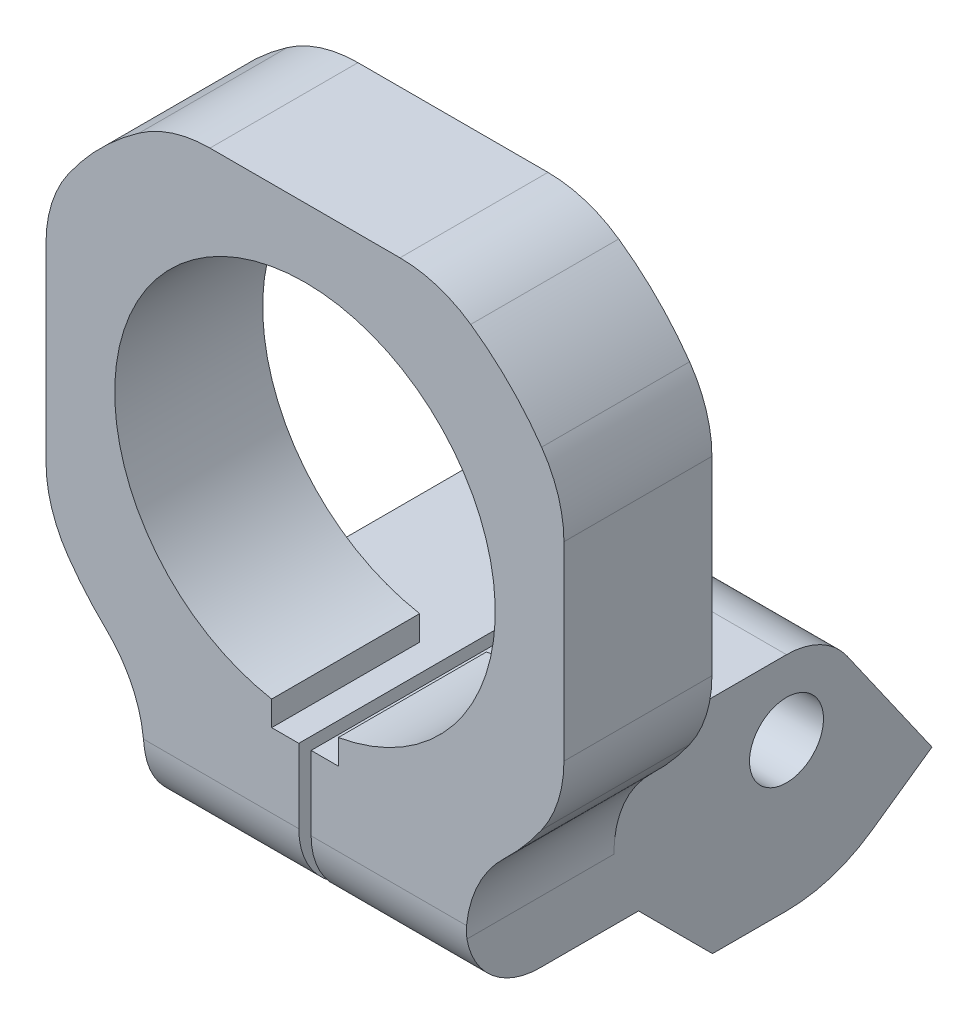
SolidWorks part; units mm, degrees
ref_plane "Front Plane" through (0, 0, 0) normal (0, 0, 1) x (1, 0, 0)
ref_plane "Top Plane" through (0, 0, 0) normal (0, 1, 0) x (1, 0, 0)
ref_plane "Right Plane" through (0, 0, 0) normal (1, 0, 0) x (0, 0, -1)
sketch "Sketch1" plane through (0, 0, 0) normal (0, 0, 1) x (1, 0, 0)
  line L0 (0, 11.4873) -> (0, -15.0157) construction
  line L1 (1.35, -8.5) -> (6.5239, -8.5)
  line L2 (1.35, -8.5) -> (-1.35, -8.5)
  line L3 (1.35, -8.5) -> (1.35, -7.4944)
  line L4 (1.35, -7.4944) -> (-1.35, -7.4944)
  line L5 (-1.35, -8.5) -> (-1.35, -7.4944)
  line L6 (1.35, -8.5) -> (-1.35, -7.4944) construction
  line L7 (1.35, -7.4944) -> (-1.35, -8.5) construction
  line L8 (-1.35, -8.5) -> (-6.5239, -8.5)
  line L9 (-1.35, -8.5) -> (-1.35, -14.6)
  line L10 (-1.35, -14.6) -> (-6.5239, -14.6)
  line L11 (-6.5239, -8.5) -> (-6.5239, -14.6)
  line L12 (1.35, -8.5) -> (1.35, -14.6)
  line L13 (-8.5, -8.5) -> (-1.25, -8.5)
  line L14 (-1.25, -8.5) -> (-1.25, -7.5117)
  line L15 (1.25, -7.5117) -> (1.25, -8.5)
  line L16 (1.25, -8.5) -> (8.5, -8.5)
  line L17 (8.5, -8.5) -> (8.5, -2.45)
  line L18 (8.5, -2.45) -> (10, -2.45)
  line L19 (10, 2.45) -> (8.5, 2.45)
  line L20 (8.5, 2.45) -> (8.5, 8.5)
  line L21 (8.5, 8.5) -> (-8.5, 8.5)
  line L22 (-8.5, 8.5) -> (-8.5, 2.45)
  line L23 (-8.5, 2.45) -> (-10, 2.45)
  line L24 (-10, -2.45) -> (-8.5, -2.45)
  line L25 (-8.5, -2.45) -> (-8.5, -8.5)
  line L26 (-8.5, -8.5) -> (-1.25, -8.5)
  line L27 (-1.25, -8.5) -> (-1.25, -7.5117)
  line L28 (1.25, -7.5117) -> (1.25, -8.5)
  line L29 (1.25, -8.5) -> (8.5, -8.5)
  line L30 (8.5, -8.5) -> (8.5, -2.45)
  line L31 (8.5, -2.45) -> (10, -2.45)
  line L32 (10, 2.45) -> (8.5, 2.45)
  line L33 (8.5, 2.45) -> (8.5, 8.5)
  line L34 (8.5, 8.5) -> (-8.5, 8.5)
  line L35 (-8.5, 8.5) -> (-8.5, 2.45)
  line L36 (-8.5, 2.45) -> (-10, 2.45)
  line L37 (-10, -2.45) -> (-8.5, -2.45)
  line L38 (-8.5, -2.45) -> (-8.5, -8.5)
  line L39 (1.35, -14.6) -> (6.5239, -14.6)
  line L40 (6.5239, -8.5) -> (6.5239, -14.6)
  line L41 (-1.25, -8.0059) -> (-1.35, -8.0059) construction
  line L42 (-1.35, -14.6) -> (-0.25, -14.6)
  line L43 (-1.35, -14.6) -> (-1.35, -8.6)
  line L44 (-1.35, -8.6) -> (-0.25, -8.6)
  line L45 (-0.25, -14.6) -> (-0.25, -8.6)
  line L46 (7.715, 0) -> (7.615, 0) construction
  line L47 (-1.25, -8.5) -> (-1.25, -8.6) construction
  line L48 (-1.35, -8.5) -> (1.35, -8.5)
  line L49 (-1.35, -8.5) -> (-1.35, -8.6)
  line L50 (-1.35, -8.6) -> (1.35, -8.6)
  line L51 (1.35, -8.5) -> (1.35, -8.6)
  line L52 (1.35, -8.6) -> (0.25, -8.6)
  line L53 (0.25, -14.6) -> (0.25, -8.6)
  line L54 (1.35, -14.6) -> (0.25, -14.6)
  circle A0 centre (0, 0) radius 7.715
  circle A1 centre (0, 0) radius 10.715
  arc A3 (1.25, -7.5117) -> (-1.25, -7.5117) centre (0, 0) ccw
  arc A4 (10, -2.45) -> (10, 2.45) centre (10, 0) ccw
  arc A5 (-10, 2.45) -> (-10, -2.45) centre (-10, 0) ccw
  arc A6 (1.25, -7.5117) -> (-1.25, -7.5117) centre (0, 0) ccw
  arc A7 (10, -2.45) -> (10, 2.45) centre (10, 0) ccw
  arc A8 (-10, 2.45) -> (-10, -2.45) centre (-10, 0) ccw
  point P10 (0, -7.9972)
  dimension "D2" = 0.1
  dimension "D4" = 3
  dimension "D3" = 0.5
  dimension "D5" = 6
  dimension "D1" = 0
extrude "Shape" add sketch "Sketch1" along normal blind 6 contours L36 A8 L37 L38 L26 L27 A0 L28 L29 L30 L31 A7 L32 L33 L34 L35 | A7 A1 L33 L32 | A7 L31 L30 A1 | A8 A1 L38 L37 | A8 L36 L35 A1 | L34 A1 | L8 A1 L9 | L12 A1 L1 | A1 L12 L39 L40 | A1 L11 L10 L9 | L9 A1 L45 L44 | A1 L43 L42 L45 | A1 L53 L54 L12 | L53 A1 L12 L50 region at (1.6235, -8.048, 0) region at (3.2599, -9.3092, 0) region at (4.1264, -12.177, 0) region at (0.7964, -9.6403, 0) region at (0.8019, -12.6401, 0) region at (9.2085, -3.9179, 0) region at (-3.2599, -9.3092, 0) region at (-0.7964, -9.6403, 0) region at (-0.8019, -12.6401, 0) region at (9.2085, 3.9179, 0) region at (-4.1264, -12.177, 0) region at (-9.2085, -3.9179, 0) region at (0, 9.3944, 0) region at (-9.2085, 3.9179, 0)
sketch "Sketch3" plane through (0, 0, 0) normal (0, 0, -1) x (-1, 0, 0)
  line L1 (-6.5239, -14.6) -> (-0.25, -14.6)
  line L2 (-6.5239, -14.6) -> (-6.5239, -8.6)
  line L3 (-6.5239, -8.6) -> (-0.25, -8.6)
  line L4 (-0.25, -14.6) -> (-0.25, -8.6)
  line L5 (6.5239, -14.6) -> (0.25, -14.6)
  line L6 (6.5239, -14.6) -> (6.5239, -8.6)
  line L7 (6.5239, -8.6) -> (0.25, -8.6)
  line L8 (0.25, -14.6) -> (0.25, -8.6)
extrude "Lever" add sketch "Sketch3" along normal blind 10
sketch "Sketch2" plane through (6.5239, 0, 0) normal (1, 0, 0) x (0, 0, -1)
  line L0 (-6, -11.6) -> (10, -11.6) construction
  line L4 (10, -8.6) -> (0, -8.6) construction
  line L5 (10, -8.6) -> (-6, -8.6)
  line L6 (10, -8.6) -> (10, -14.6)
  line L7 (10, -14.6) -> (-6, -14.6)
  line L8 (-6, -8.6) -> (-6, -14.6)
  circle A0 centre (7, -11.6) radius 3
  circle A1 centre (7, -11.6) radius 1.5
  circle A2 centre (-3, -11.6) radius 3
  line M4 (-6, -14.6) -> (10, -14.6)
  line M9 (10, -14.6) -> (10, -8.6)
  line M10 (10, -8.6) -> (0, -8.6)
  dimension "D1" = 3
extrude "Cuts" cut sketch "Sketch2" against normal up to surface (13.0478 mm away) contours A0 L6 M10 | A0 L7 M9 | L0 A1 | A1 L0 | A2 L8 M4 region at (6.5239, -13.9299, 5.3299) region at (6.5239, -13.9299, -9.3299) region at (6.5239, -10.9634, -7) region at (6.5239, -12.2366, -7) region at (6.5239, -9.2701, -9.3299) up to face at (-6.5239, -10.5667, -1.3333)
sketch "Sketch5" plane through (-6.5239, 0, 0) normal (-1, 0, 0) x (0, 0, 1)
  line L0 (-7, -17.6) -> (-4, -17.6)
  line L1 (-4, -17.6) -> (-4, -14.6)
  line L2 (3, -14.6) -> (-7, -14.6) construction
  line L3 (-7, -11.6) -> (-10.4415, -16.5149)
  line L4 (-7, -11.6) -> (-7, -14.6) construction
  line L5 (-10.4415, -16.5149) -> (-12.8989, -14.7942)
  line L6 (-12.8989, -14.7942) -> (-9.4575, -9.8793)
  line L7 (-7, -17.6) -> (-7, -14.6)
  line L8 (-4, -17.6) -> (-1, -14.6)
  circle A0 centre (-7, -11.6) radius 6
  arc A1 (-7, -8.6) -> (-7, -14.6) centre (-7, -11.6) ccw construction
  arc M8 (-7, -8.6) -> (-7, -14.6) centre (-7, -11.6) ccw
  line M9 (-7, -14.6) -> (3, -14.6)
  dimension "D1" = 12
  dimension "D2" = 45
  dimension "D3" = 35
extrude "Limits 1" add sketch "Sketch5" against normal up to surface (6.2739 mm away) contours A0 L0 L1 | L7 A0 L1 M9 | L6 A0 L3 M8 | A0 L6 L5 | L3 A0 L7 M8 | A0 L1 L8 M9 | L1 A0 M9 region at (-6.5239, -17.3619, -4.7396) region at (-6.5239, -15.9818, -8.3816) region at (-6.5239, -15.9801, -5.5723) region at (-6.5239, -15.9486, -2.6514) region at (-6.5239, -13.951, -10.5987) region at (-6.5239, -15.0233, -12.1565) region at (-6.5239, -15.3955, -3.2045) up to face at (-0.25, -11.6, -5.5)
sketch "Sketch6" plane through (6.5239, 0, 0) normal (1, 0, 0) x (0, 0, -1)
  line L0 (-3, -14.6) -> (7, -14.6) construction
  line L1 (-3, -14.6) -> (7, -14.6)
  line L7 (-3, -14.6) -> (1, -14.6)
  line L8 (1, -14.6) -> (4, -17.6)
  line L9 (4, -17.6) -> (7, -17.6)
  line L10 (10.4415, -16.5149) -> (12.8989, -14.7942)
  line L11 (12.8989, -14.7942) -> (9.4575, -9.8793)
  line L12 (7, -8.6) -> (-6, -8.6)
  line L13 (-6, -8.6) -> (-6, -11.6)
  line L14 (-3, -14.6) -> (1, -14.6)
  line L15 (1, -14.6) -> (4, -17.6)
  line L16 (4, -17.6) -> (7, -17.6)
  line L17 (10.4415, -16.5149) -> (12.8989, -14.7942)
  line L18 (12.8989, -14.7942) -> (9.4575, -9.8793)
  line L19 (7, -8.6) -> (-6, -8.6)
  line L20 (-6, -8.6) -> (-6, -11.6)
  arc A0 (7, -14.6) -> (7, -8.6) centre (7, -11.6) ccw construction
  arc A1 (7, -14.6) -> (7, -8.6) centre (7, -11.6) ccw
  arc A3 (7, -17.6) -> (10.4415, -16.5149) centre (7, -11.6) ccw
  arc A4 (9.4575, -9.8793) -> (7, -8.6) centre (7, -11.6) ccw
  arc A5 (-6, -11.6) -> (-3, -14.6) centre (-3, -11.6) ccw
  arc A6 (7, -17.6) -> (10.4415, -16.5149) centre (7, -11.6) ccw
  arc A7 (9.4575, -9.8793) -> (7, -8.6) centre (7, -11.6) ccw
  arc A8 (-6, -11.6) -> (-3, -14.6) centre (-3, -11.6) ccw
  arc M13 (7, -14.6) -> (7, -8.6) centre (7, -11.6) ccw
  dimension "D1" = 0
extrude "Limits 2" add sketch "Sketch6" against normal up to surface (6.2739 mm away) contours L16 A6 L17 L18 L1 M13 region at (6.5239, -15.3081, -7.6258) up to face at (0.25, -13.1, -7)
sketch "Sketch8" plane through (0, 0, 6) normal (0, 0, 1) x (1, 0, 0)
  line L1 (-9.5, -9.5) -> (9.5, -9.5)
  line L2 (-9.5, -9.5) -> (-9.5, 9.5)
  line L3 (-9.5, 9.5) -> (9.5, 9.5)
  line L4 (9.5, -9.5) -> (9.5, 9.5)
  line L5 (-9.5, -9.5) -> (9.5, 9.5) construction
  line L6 (-9.5, 9.5) -> (9.5, -9.5) construction
  line L7 (-10.715, -10.715) -> (10.715, -10.715)
  line L8 (-10.715, -10.715) -> (-10.715, 10.715)
  line L9 (-10.715, 10.715) -> (10.715, 10.715)
  line L10 (10.715, -10.715) -> (10.715, 10.715)
  line L11 (-10.715, -10.715) -> (10.715, 10.715) construction
  line L12 (-10.715, 10.715) -> (10.715, -10.715) construction
  arc A0 (6.5239, -8.5) -> (-6.5239, -8.5) centre (0, 0) ccw construction
  point P0 (0, 0)
  point P6 (0, 0)
  arc M16 (6.5239, -8.5) -> (-6.5239, -8.5) centre (0, 0) ccw
  dimension "D1" = 19
extrude "Cut-Extrude2" cut sketch "Sketch8" against normal up to next contours L3 M16 | L2 M16 | L4 M16 region at (-9.9884, 0, 6) region at (9.9884, 0, 6) region at (0, 9.9884, 6)
sketch "Sketch9" plane through (0, 0, 6) normal (0, 0, 1) x (1, 0, 0)
  line L9 (-7.1328, -9.2933) -> (-6.5239, -9.7606)
  line L10 (-6.5239, -8.5) -> (-6.5239, -11.6) construction
  line L11 (7.1328, -9.2933) -> (6.5239, -9.7606)
  line L12 (-10.5, 5.1953) -> (-10.5, -5.1953)
  line L13 (5.1953, 10.5) -> (-5.1953, 10.5)
  line L14 (10.5, -5.1953) -> (10.5, 5.1953)
  line L15 (-10.5, 5.1953) -> (-10.5, -5.1953)
  line L16 (5.1953, 10.5) -> (-5.1953, 10.5)
  line L17 (10.5, -5.1953) -> (10.5, 5.1953)
  line L18 (6.5239, -8.5) -> (6.5239, -11.6) construction
  line L32 (-9.5, 4.9559) -> (-9.5, -4.9559)
  line L33 (-6.5239, -8.5) -> (-6.5239, -11.6)
  line L34 (-6.5239, -11.6) -> (-0.25, -11.6)
  line L35 (-0.25, -11.6) -> (-0.25, -8.6)
  line L36 (-0.25, -8.6) -> (-1.35, -8.6)
  line L37 (-1.35, -8.6) -> (-1.35, -7.596)
  line L38 (1.35, -7.596) -> (1.35, -8.6)
  line L39 (1.35, -8.6) -> (0.25, -8.6)
  line L40 (0.25, -8.6) -> (0.25, -11.6)
  line L41 (0.25, -11.6) -> (6.5239, -11.6)
  line L42 (6.5239, -11.6) -> (6.5239, -8.5)
  line L43 (9.5, -4.9559) -> (9.5, 4.9559)
  line L44 (4.9559, 9.5) -> (-4.9559, 9.5)
  line L45 (-9.5, 4.9559) -> (-9.5, -4.9559)
  line L46 (-6.5239, -8.5) -> (-6.5239, -11.6)
  line L47 (-6.5239, -11.6) -> (-0.25, -11.6)
  line L48 (-0.25, -11.6) -> (-0.25, -8.6)
  line L49 (-0.25, -8.6) -> (-1.35, -8.6)
  line L50 (-1.35, -8.6) -> (-1.35, -7.596)
  line L51 (1.35, -7.596) -> (1.35, -8.6)
  line L52 (1.35, -8.6) -> (0.25, -8.6)
  line L53 (0.25, -8.6) -> (0.25, -11.6)
  line L54 (0.25, -11.6) -> (6.5239, -11.6)
  line L55 (6.5239, -11.6) -> (6.5239, -8.5)
  line L56 (9.5, -4.9559) -> (9.5, 4.9559)
  line L57 (4.9559, 9.5) -> (-4.9559, 9.5)
  arc A13 (-10.5, -5.1953) -> (-7.1328, -9.2933) centre (0, 0) ccw
  arc A14 (7.1328, -9.2933) -> (10.5, -5.1953) centre (0, 0) ccw
  arc A15 (-5.1953, 10.5) -> (-10.5, 5.1953) centre (0, 0) ccw
  arc A16 (10.5, 5.1953) -> (5.1953, 10.5) centre (0, 0) ccw
  arc A17 (-10.5, -5.1953) -> (-7.1328, -9.2933) centre (0, 0) ccw
  arc A18 (7.1328, -9.2933) -> (10.5, -5.1953) centre (0, 0) ccw
  arc A19 (-5.1953, 10.5) -> (-10.5, 5.1953) centre (0, 0) ccw
  arc A20 (10.5, 5.1953) -> (5.1953, 10.5) centre (0, 0) ccw
  arc A22 (-9.5, -4.9559) -> (-6.5239, -8.5) centre (0, 0) ccw
  arc A23 (1.35, -7.596) -> (-1.35, -7.596) centre (0, 0) ccw
  arc A24 (6.5239, -8.5) -> (9.5, -4.9559) centre (0, 0) ccw
  arc A25 (9.5, 4.9559) -> (4.9559, 9.5) centre (0, 0) ccw
  arc A26 (-4.9559, 9.5) -> (-9.5, 4.9559) centre (0, 0) ccw
  arc A27 (-9.5, -4.9559) -> (-6.5239, -8.5) centre (0, 0) ccw
  arc A28 (1.35, -7.596) -> (-1.35, -7.596) centre (0, 0) ccw
  arc A29 (6.5239, -8.5) -> (9.5, -4.9559) centre (0, 0) ccw
  arc A30 (9.5, 4.9559) -> (4.9559, 9.5) centre (0, 0) ccw
  arc A31 (-4.9559, 9.5) -> (-9.5, 4.9559) centre (0, 0) ccw
  line M8 (-9.5, 4.9559) -> (-9.5, -4.9559)
  arc M9 (-9.5, -4.9559) -> (-6.5239, -8.5) centre (0, 0) ccw
  line M10 (-6.5239, -8.5) -> (-6.5239, -11.6)
  line M20 (6.5239, -11.6) -> (6.5239, -8.5)
  arc M21 (6.5239, -8.5) -> (9.5, -4.9559) centre (0, 0) ccw
  line M22 (9.5, -4.9559) -> (9.5, 4.9559)
  arc M23 (9.5, 4.9559) -> (4.9559, 9.5) centre (0, 0) ccw
  line M24 (4.9559, 9.5) -> (-4.9559, 9.5)
  arc M25 (-4.9559, 9.5) -> (-9.5, 4.9559) centre (0, 0) ccw
  dimension "D1" = 1
  dimension "D2" = 0
extrude "Boss-Extrude1" add sketch "Sketch9" against normal up to surface (6 mm away) contours L17 A20 L16 A19 L15 A17 L9 L11 A18 M10 M9 M8 M25 M24 M23 M22 M21 M20 region at (-8.8259, -7.2521, 6) up to face at (0, -2.2792, 0)
fillet "Fillet1" radius 5 8 edges at (-6.5239, -9.7606, 3) (-10.5, -5.1953, 3) (-10.5, 5.1953, 3) (-5.1953, 10.5, 3) (5.1953, 10.5, 3) (10.5, 5.1953, 3) (10.5, -5.1953, 3) (6.5239, -9.7606, 3)
